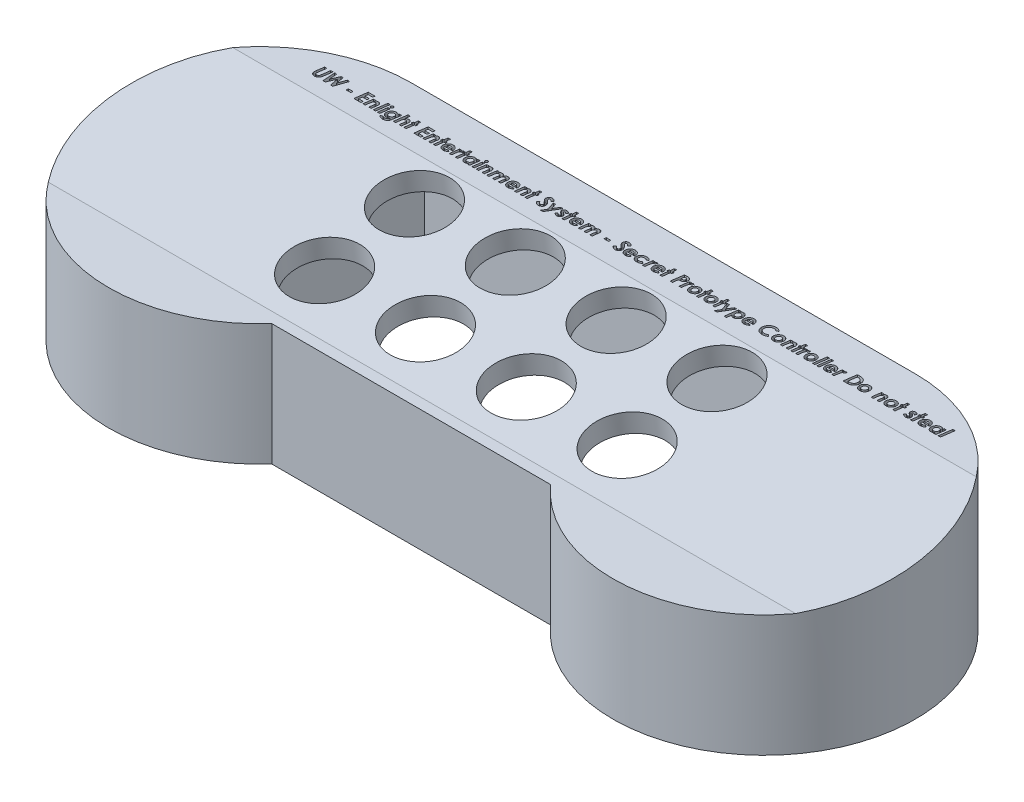
SolidWorks part; units mm, degrees
ref_plane "Front Plane" through (0, 0, 0) normal (0, 0, 1) x (1, 0, 0)
ref_plane "Top Plane" through (0, 0, 0) normal (0, 1, 0) x (1, 0, 0)
ref_plane "Right Plane" through (0, 0, 0) normal (1, 0, 0) x (0, 0, -1)
sketch "Sketch1" plane through (0, 0, 0) normal (0, 1, 0) x (1, 0, 0)
  line L3 (85.5, 30.2918) -> (-41.5, 30.2918)
  line L7 (-13.1019, -33.2082) -> (57.1019, -33.2082)
  line L8 (-63.3461, -39.0229) -> (-76.3578, -44.5347) construction
  line L9 (-41.5, -7.8082) -> (-79.6, -7.8082) construction
  line L10 (85.5, -7.8082) -> (123.6, -7.8082) construction
  arc A0 (-41.5, 30.2918) -> (-13.1019, -33.2082) centre (-41.5, -7.8082) ccw
  arc A1 (57.1019, -33.2082) -> (85.5, 30.2918) centre (85.5, -7.8082) ccw
  point P0 (0, 0)
  dimension "D4" = 76.2
  dimension "D2" = 127
  dimension "D1" = 38.1
  dimension "D3" = 63.5
extrude "Boss-Extrude1" add sketch "Sketch1" along normal blind 40.4
sketch "Sketch3" plane through (0, 0, 0) normal (1, 0, 0) x (0, 0, -1)
  line L2 (30.2918, 37.2179) -> (15.5, 37.2179)
  line L3 (30.2918, 40.4) -> (30.2918, 0) construction
  line L10 (55, 0) -> (-55, 0) construction
  line L14 (-30.5, 56.6478) -> (30.2918, 56.6478)
  line L15 (30.2918, 56.6478) -> (30.2918, 37.2179)
  line L18 (-56.0906, 56.6478) -> (-30.5, 56.6478)
  line L19 (15.5, 37.2179) -> (-30.5, 30.6308)
  line L20 (-30.5, 30.6308) -> (-56.0906, 30.6308)
  line L21 (-56.0906, 56.6478) -> (-56.0906, 30.6308)
  dimension "D1" = 37.2179
extrude "Cut-Extrude2" cut sketch "Sketch3" along normal through all both and the other way through all
sketch "Sketch2" plane through (0, 0, 0) normal (0, 1, 0) x (1, 0, 0)
  line L6 (85.5, 25.2918) -> (-41.5, 25.2918)
  line L7 (-15.4337, -28.2082) -> (59.4337, -28.2082)
  line L8 (85.5, 25.2918) -> (-41.5, 25.2918)
  line L9 (-15.4337, -28.2082) -> (59.4337, -28.2082)
  arc A8 (59.4337, -28.2082) -> (85.5, 25.2918) centre (85.5, -7.8082) ccw
  arc A9 (-41.5, 25.2918) -> (-15.4337, -28.2082) centre (-41.5, -7.8082) ccw
  arc A10 (59.4337, -28.2082) -> (85.5, 25.2918) centre (85.5, -7.8082) ccw
  arc A11 (-41.5, 25.2918) -> (-15.4337, -28.2082) centre (-41.5, -7.8082) ccw
  dimension "D1" = 5
extrude "Cut-Extrude3" cut sketch "Sketch2" along normal blind 5
sketch "Sketch4" plane through (0, 0, 0) normal (1, 0, 0) x (0, 0, -1)
  line L1 (22.6718, 32.1379) -> (15.5, 32.1379)
  line L4 (30.2918, 37.2179) -> (15.5, 37.2179) construction
  line L6 (22.6718, 5) -> (22.6718, 32.1379)
  line L7 (22.6718, 5) -> (-29.6351, 5)
  line L8 (15.5, 32.1379) -> (-29.6351, 25.5138)
  line L9 (15.5, 37.2179) -> (-30.5, 30.6308) construction
  line L11 (30.2918, 37.2179) -> (30.2918, 0) construction
  line L13 (-29.6351, 25.5138) -> (-29.6351, 5)
  dimension "D1" = 5.08
  dimension "D2" = 0.2
  dimension "D4" = 7.62
extrude "Cut-Extrude4" cut sketch "Sketch4" along normal blind 76.2 and the other way blind 30.48
sketch "Sketch5" plane through (0, 0, -30.2918) normal (0, 0, -1) x (-1, 0, 0)
  line L1 (41.91, 0) -> (-41.91, 0) construction
  line L5 (-85.5, 37.2179) -> (-85.5, 0) construction
  line L6 (41.5, 37.2179) -> (41.5, 0) construction
  circle A3 centre (-34.7, 0) radius 5.08
  circle A4 centre (3.4, 0) radius 5.08
  circle A5 centre (-9.3, 0) radius 5.08
  point P10 (-85.5, 18.6089)
  dimension "D1" = 50.8
  dimension "D2" = 50.8
  dimension "D3" = 38.1
  dimension "D4" = 12.7
extrude "Cut-Extrude5" cut sketch "Sketch5" against normal blind 7.62
sketch "Sketch6" plane through (0, 37.2179, 0) normal (0, 1, 0) x (1, 0, 0)
  text T0 "<b><i>UW - Enlight Entertainment System - Secret Prototype Controller Do not steal</i></b>"
  dimension "D1" = 15.24
extrude "Cut-Extrude6" cut sketch "Sketch6" against normal blind 1.27
sketch "Sketch9" plane through (0, 34.2951, 4.911) normal (0, 0.9899, 0.1418) x (1, 0, 0)
  circle A4 centre (-16.1, -12.1275) radius 8.9662
  circle A6 centre (-16.1, 10.7325) radius 8.9662
  circle A8 centre (9.3, 10.7325) radius 8.9662
  circle A9 centre (9.3, -12.1275) radius 8.9662
  circle A10 centre (60.1, -12.1275) radius 8.9662
  circle A11 centre (34.7, -12.1275) radius 8.9662
  circle A12 centre (34.7, 10.7325) radius 8.9662
  circle A13 centre (60.1, 10.7325) radius 8.9662
  ellipse E2 centre (85.5, -2.9268) end of major axis (85.5, -41.4154) minor radius 38.1 (116.1054, -25.85) -> (115.6386, 20.6192) ccw construction
  ellipse E3 centre (-41.5, -2.9268) end of major axis (-41.5, -41.4154) minor radius 38.1 (-71.6386, 20.6192) -> (-72.1054, -25.85) ccw construction
  dimension "D1" = 22.86
  dimension "D7" = 25.4
  dimension "D6" = 25.4
  dimension "D2" = 2
  dimension "D3" = 2
  dimension "D4" = 25.4
  dimension "D5" = 25.4
  dimension "D8" = 25.4
extrude "Cut-Extrude8" cut sketch "Sketch9" against normal blind 50.8
